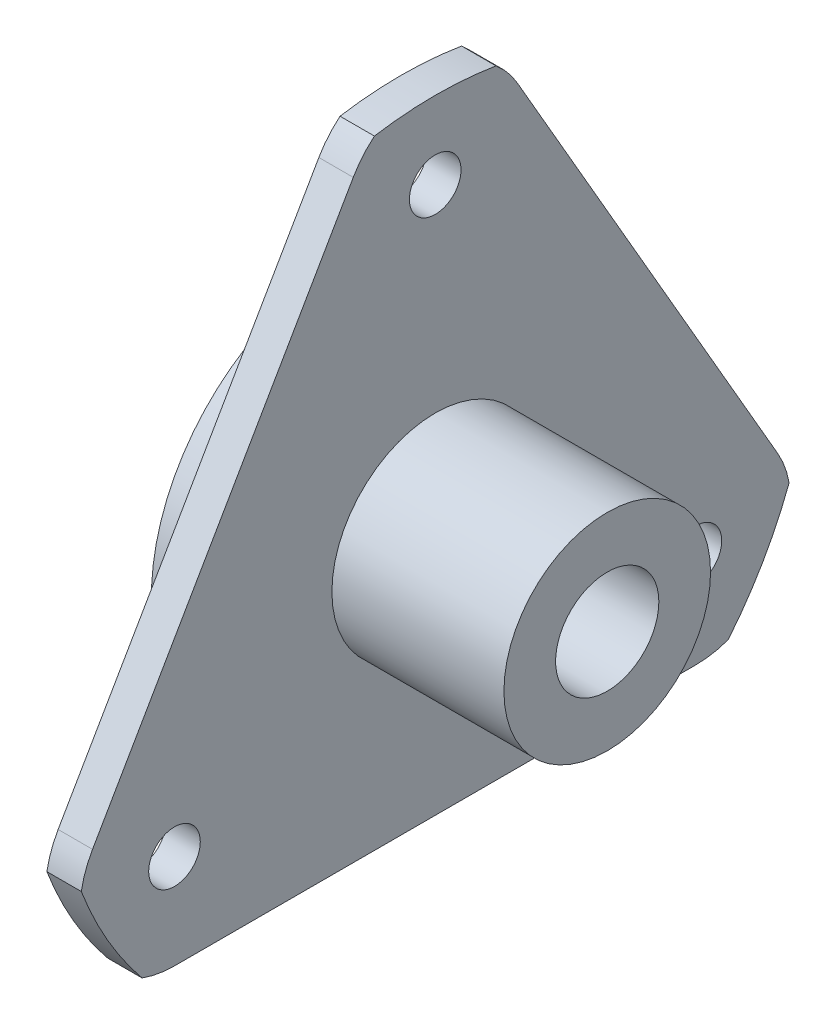
SolidWorks part; units mm, degrees
material "1023 Arkusz stali węglowej (SS)"
ref_plane "Płaszczyzna przednia" through (0, 0, 0) normal (0, 0, 1) x (1, 0, 0)
ref_plane "Płaszczyzna górna" through (0, 0, 0) normal (0, 1, 0) x (1, 0, 0)
ref_plane "Płaszczyzna prawa" through (0, 0, 0) normal (1, 0, 0) x (0, 0, -1)
sketch "Szkic2" plane through (0, 0, 0) normal (0, 0, 1) x (1, 0, 0)
  line L0 (0, 0) -> (-30, 0) construction
  line L23 (0, 6) -> (-30, 6)
  line L24 (-24, 23) -> (-30, 23)
  line L25 (-24, 44) -> (-24, 23)
  line L26 (-24, 44) -> (-20, 44)
  line L27 (0, 6) -> (0, 12.0108)
  line L28 (-20, 12.0108) -> (0, 12.0108)
  line L29 (-20, 44) -> (-20, 12.0108)
  line L30 (-30, 6) -> (-30, 23)
revolve "Obrót1" add sketch "Szkic2" angle 360 about L0
sketch "Szkic3" plane through (-24, 0, 0) normal (-1, 0, 0) x (0, 0, 1)
  line L0 (-39.8372, -12) -> (-9.5263, 40.5)
  line L1 (9.5263, 40.5) -> (39.8372, -12)
  line L2 (30.3109, -28.5) -> (-30.3109, -28.5)
  circle A0 centre (0, 35) radius 3
  circle A1 centre (30.3109, -17.5) radius 3
  circle A2 centre (-30.3109, -17.5) radius 3
  arc A3 (9.5263, 40.5) -> (-9.5263, 40.5) centre (0, 35) ccw
  arc A4 (30.3109, -28.5) -> (39.8372, -12) centre (30.3109, -17.5) ccw
  arc A5 (-39.8372, -12) -> (-30.3109, -28.5) centre (-30.3109, -17.5) ccw
  circle A6 centre (0, 0) radius 52.403
  point P9 (0, 0)
  point P16 (0, 0)
  point P24 (0, 0)
  point P28 (0, 0)
  circle M2 centre (0, 0) radius 44
  dimension "D1" = 6
  dimension "D4" = 22
  dimension "D2" = 35
  dimension "D3" = 3
extrude "Wytnij-wyciągnięcie1" cut sketch "Szkic3" against normal through all contours A6 A5 A3 A4 M2 | A5 L0 A3 M2 | A0 | A2 | A4 A3 L1 M2 | A5 A4 L2 M2 | A1 region at (-24, 17.3964, -30.1314) region at (-24, -34.7928, 0) region at (-24, 17.3964, 30.1314) region at (-24, 35, 0) region at (-24, -17.5, -30.3109) region at (-24, 0, -50.9208)
